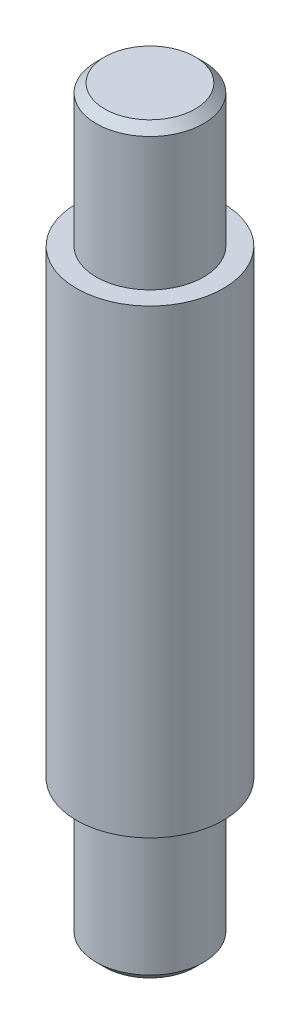
SolidWorks part; units mm, degrees
ref_plane "Front Plane" through (0, 0, 0) normal (0, 0, 1) x (1, 0, 0)
ref_plane "Top Plane" through (0, 0, 0) normal (0, 1, 0) x (1, 0, 0)
ref_plane "Right Plane" through (0, 0, 0) normal (1, 0, 0) x (0, 0, -1)
sketch "Sketch1" plane through (0, 0, 0) normal (1, 0, 0) x (0, 0, -1)
  line L0 (0, -33.401) -> (0, 33.401) construction
  line L1 (0, 33.401) -> (-4.064, 33.401)
  line L2 (-4.826, 32.639) -> (-4.826, 20.701)
  line L3 (-4.826, 20.701) -> (-6.604, 20.701)
  line L4 (-6.604, 20.701) -> (-6.604, -20.701)
  line L5 (-6.604, -20.701) -> (-4.826, -20.701)
  line L6 (-4.826, -20.701) -> (-4.826, -32.639)
  line L7 (-4.064, -33.401) -> (0, -33.401)
  line L8 (-15.6281, 0) -> (29.047, 0) construction
  line L9 (-4.064, 33.401) -> (-4.826, 32.639)
  line L10 (-4.826, -32.639) -> (-4.064, -33.401)
  line L11 (0, 33.401) -> (0, -33.401)
  point P4 (0, 0)
  point P6 (-4.826, 33.401)
  point P11 (-4.826, -33.401)
  dimension "D1" = 66.802
  dimension "D2" = 41.402
  dimension "D3" = 4.826
  dimension "D4" = 6.604
  dimension "D5" = 0.762
  dimension "D6" = 45
  dimension "D7" = 0.762
  dimension "D8" = 45
  dimension "D9" = 4.826
  dimension "D10" = 12.7
revolve "Revolve1" add sketch "Sketch1" angle 360 about L11
